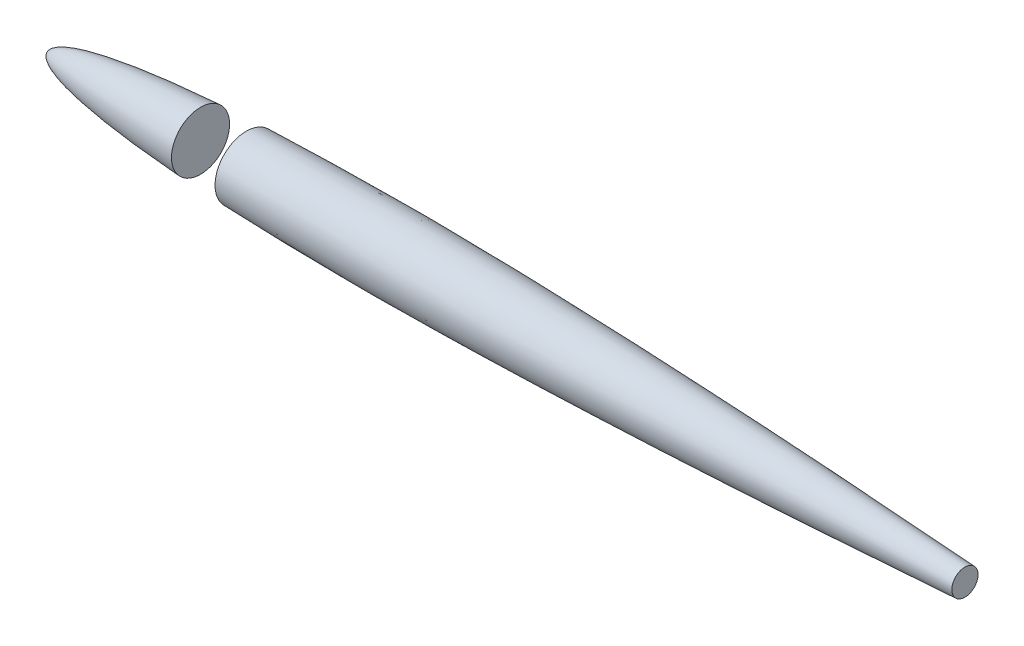
SolidWorks part; units mm, degrees
ref_plane "Front Plane" through (0, 0, 0) normal (0, 0, 1) x (1, 0, 0)
ref_plane "Top Plane" through (0, 0, 0) normal (0, 1, 0) x (1, 0, 0)
ref_plane "Right Plane" through (0, 0, 0) normal (1, 0, 0) x (0, 0, -1)
sketch "rootSketch" plane through (0, 0, 0) normal (0, 1, 0) x (1, 0, 0)
  line L0 (0, 0) -> (12000, 0) construction
  line L1 (2750, -330) -> (2750, 330) construction
  line L2 (0, 0) -> (11000, 0)
  spline S0 degree 4 poles (0, 0) (0.0002, 1.4166) (0.1225, 4.2408) (0.6739, 8.4547) (2.1097, 13.9385) (4.13, 19.1147) (6.6109, 23.9643) (9.9914, 29.3681) (13.8074, 34.3715) (18.0051, 39.0824) (24.0066, 45.0125) (32.3839, 52.2354) (43.384, 60.1944) (57.0761, 68.6181) (73.983, 77.7243) (92.7893, 86.6435) (113.9578, 95.5167) (137.4556, 104.3111) (166.2995, 114.136) (201.291, 124.8338) (243.0702, 136.2047) (291.673, 147.964) (341.2433, 158.778) (390.608, 168.603) (439.7192, 177.609) (500.6517, 187.9807) (573.4692, 199.2826) (658.6122, 211.1866) (758.0842, 223.6079) (859.6848, 234.9957) (963.387, 245.4645) (1069.1706, 255.1028) (1175.0326, 263.8354) (1280.9578, 271.7615) (1386.9346, 278.9616) (1492.954, 285.5022) (1625.577, 292.9263) (1784.8272, 300.7239) (1970.7211, 308.3762) (2183.2661, 315.3874) (2395.8558, 320.8604) (2608.4762, 324.9557) (2821.1167, 327.8069) (3033.7692, 329.5269) (3299.5919, 330.3841) (3618.5808, 329.5138) (3990.7204, 326.0523) (4415.9852, 319.2091) (4841.2016, 309.8574) (5266.3634, 298.3074) (5691.4677, 284.8151) (6116.5132, 269.5907) (6541.4998, 252.8057) (6966.4276, 234.5973) (7391.2968, 215.0715) (7816.1072, 194.3061) (8187.764, 175.0965) (8506.2884, 157.9049) (8771.6988, 143.0951) (8984.0106, 130.9561) (9196.3055, 118.5234) (9382.048, 107.3844) (9541.2445, 97.6474) (9673.9002, 89.4049) (9780.02, 82.7331) (9912.6633, 74.2947) (10032.035, 66.5803) (10138.1364, 59.6277) (10230.971, 53.4713) (10284.0168, 49.9324) (10337.0641, 46.3721) (10390.1043, 42.7909) (10443.153, 39.1874) (10496.1834, 35.5635) (10549.2402, 31.9155) (10602.2495, 28.2488) (10655.3329, 24.5543) (10708.2897, 20.8463) (10761.4536, 17.1004) (10814.2582, 13.3575) (10861.0394, 10.0201) (10900.2084, 7.2123) (10934.3368, 4.7545) (10958.871, 2.9835) (10991.7181, 0.6028) (11015.0262, -1.0918) (11049.9588, -3.6388) (11071.8096, -5.2409) (11099.5819, -7.2784) (11124.1625, -9.0892) (11155.0411, -11.3693) (11188.9639, -13.8862) (11223.5859, -16.4645) (11266.4367, -19.6696) (11318.0968, -23.5545) (11369.6077, -27.4555) (11421.2086, -31.3904) (11472.7604, -35.3439) (11524.3346, -39.3212) (11584.4862, -43.9929) (11670.4236, -50.7243) (11756.3495, -57.532) (11842.2728, -64.4184) (11928.1873, -71.3847) (11996.9163, -77.0066) (12048.459, -81.2601) (12082.8201, -84.1126) (12100, -85.543) knots 0 0 0 0 0 0.000464 0.000929 0.001393 0.001858 0.002287 0.002716 0.003486 0.003922 0.004359 0.005488 0.007118 0.008378 0.009638 0.011797 0.013955 0.015919 0.017882 0.02181 0.025978 0.030146 0.034314 0.038482 0.042518 0.046554 0.054626 0.062698 0.07077 0.079497 0.088224 0.096952 0.105679 0.114406 0.123133 0.13186 0.140587 0.158059 0.17553 0.193002 0.210474 0.227946 0.245418 0.26289 0.280362 0.315306 0.35025 0.385194 0.420137 0.455081 0.490025 0.524969 0.559913 0.594857 0.6298 0.664744 0.699688 0.71716 0.734632 0.752104 0.769576 0.787048 0.795784 0.80452 0.813256 0.821992 0.839464 0.843832 0.8482 0.852567 0.856935 0.861303 0.865671 0.870039 0.874407 0.878775 0.883143 0.887511 0.891879 0.896247 0.900615 0.902799 0.904983 0.907167 0.909351 0.912184 0.915017 0.916433 0.91785 0.920682 0.923515 0.926348 0.929181 0.932013 0.937679 0.943345 0.946177 0.94901 0.954676 0.960341 0.966007 0.977338 0.983003 0.988669 0.994334 1 1 1 1 1 construction
  spline S1 degree 4 poles (0, 0) (0.0002, 1.4166) (0.1225, 4.2408) (0.6739, 8.4547) (2.1097, 13.9385) (4.13, 19.1147) (6.6109, 23.9643) (9.9914, 29.3681) (13.8074, 34.3715) (18.0051, 39.0824) (24.0066, 45.0125) (32.3839, 52.2354) (43.384, 60.1944) (57.0761, 68.6181) (73.983, 77.7243) (92.7893, 86.6435) (113.9578, 95.5167) (137.4556, 104.3111) (166.2995, 114.136) (201.291, 124.8338) (243.0702, 136.2047) (291.673, 147.964) (341.2433, 158.778) (390.608, 168.603) (439.7192, 177.609) (500.6517, 187.9807) (573.4692, 199.2826) (658.6122, 211.1866) (758.0842, 223.6079) (859.6848, 234.9957) (963.387, 245.4645) (1069.1706, 255.1028) (1175.0326, 263.8354) (1280.9578, 271.7615) (1386.9346, 278.9616) (1492.954, 285.5022) (1625.577, 292.9263) (1784.8272, 300.7239) (1970.7211, 308.3762) (2183.2661, 315.3874) (2395.8558, 320.8604) (2608.4762, 324.9557) (2821.1167, 327.8069) (3033.7692, 329.5269) (3299.5919, 330.3841) (3618.5808, 329.5138) (3990.7204, 326.0523) (4415.9852, 319.2091) (4841.2016, 309.8574) (5266.3634, 298.3074) (5691.4677, 284.8151) (6116.5132, 269.5907) (6541.4998, 252.8057) (6966.4276, 234.5973) (7391.2968, 215.0715) (7816.1072, 194.3061) (8187.764, 175.0965) (8506.2884, 157.9049) (8771.6988, 143.0951) (8984.0106, 130.9561) (9196.3055, 118.5234) (9382.048, 107.3844) (9541.2445, 97.6474) (9673.9002, 89.4049) (9780.02, 82.7331) (9912.6633, 74.2947) (10032.035, 66.5803) (10138.1364, 59.6277) (10230.971, 53.4713) (10284.0168, 49.9324) (10337.0641, 46.3721) (10390.1043, 42.7909) (10443.153, 39.1874) (10496.1834, 35.5635) (10549.2402, 31.9155) (10602.2495, 28.2488) (10655.3329, 24.5543) (10708.2897, 20.8463) (10761.4536, 17.1004) (10814.2582, 13.3575) (10861.0394, 10.0201) (10900.2084, 7.2123) (10934.3368, 4.7545) (10958.871, 2.9835) (10981.8033, 1.3214) (10993.9727, 0.438) (11000, 0) knots 0 0 0 0 0 0.000464 0.000929 0.001393 0.001858 0.002287 0.002716 0.003486 0.003922 0.004359 0.005488 0.007118 0.008378 0.009638 0.011797 0.013955 0.015919 0.017882 0.02181 0.025978 0.030146 0.034314 0.038482 0.042518 0.046554 0.054626 0.062698 0.07077 0.079497 0.088224 0.096952 0.105679 0.114406 0.123133 0.13186 0.140587 0.158059 0.17553 0.193002 0.210474 0.227946 0.245418 0.26289 0.280362 0.315306 0.35025 0.385194 0.420137 0.455081 0.490025 0.524969 0.559913 0.594857 0.6298 0.664744 0.699688 0.71716 0.734632 0.752104 0.769576 0.787048 0.795784 0.80452 0.813256 0.821992 0.839464 0.843832 0.8482 0.852567 0.856935 0.861303 0.865671 0.870039 0.874407 0.878775 0.883143 0.887511 0.891879 0.896247 0.900615 0.902799 0.904983 0.907167 0.909351 0.909351 0.909351 0.909351 0.909351
  point P5 (2750, 0)
  dimension "rootQuarterChord" = 2750
  dimension "rootMaxThickness" = 660
revolve "Revolve1" add sketch "rootSketch" angle 360 about L0
ref_plane "Plane1" through (9020, 0, 0) normal (1, 0, 0) x (0, 0, -1)
sketch "cutSketch" plane through (9020, 0, 0) normal (1, 0, 0) x (0, 0, -1)
  circle A0 centre (0, 0) radius 330
  dimension "cutDiameter" = 660
extrude "Cut-Extrude1" cut sketch "cutSketch" along normal through all
sketch "Sketch1" plane through (0, 0, 0) normal (0, 1, 0) x (1, 0, 0)
  line L0 (0, 0) -> (1500, 0)
  line L2 (1500, 0) -> (1950, 0)
  line L3 (1500, 0) -> (1500, 1500)
  line L4 (1500, 1500) -> (1950, 1500)
  line L5 (1950, 0) -> (1950, 1500)
  dimension "D1" = 1500
  dimension "D2" = 450
  dimension "D3" = 1500
revolve "Cut-Revolve2" cut sketch "Sketch1" angle 360 about L0 region at (1725, 0, -750)
equation "\"chord\"= 11.00"
equation "\"NACAairfoil\"= 0006"
equation "\"tailCutoffPercentage\"= 0.18"
equation "\"rootQuarterChord@rootSketch\"=\"chord\"/4"
equation "\"rootMaxThickness@rootSketch\"=\"rootQuarterChord@rootSketch\"*4*\"NACAairfoil\"/100"
equation "\"cutDiameter@cutSketch\"=\"rootMaxThickness@rootSketch\""
equation "\"cutChord@Plane1\"= \"rootQuarterChord@rootSketch\" * 4 * ( 1 - \"tailCutoffPercentage\" )"
